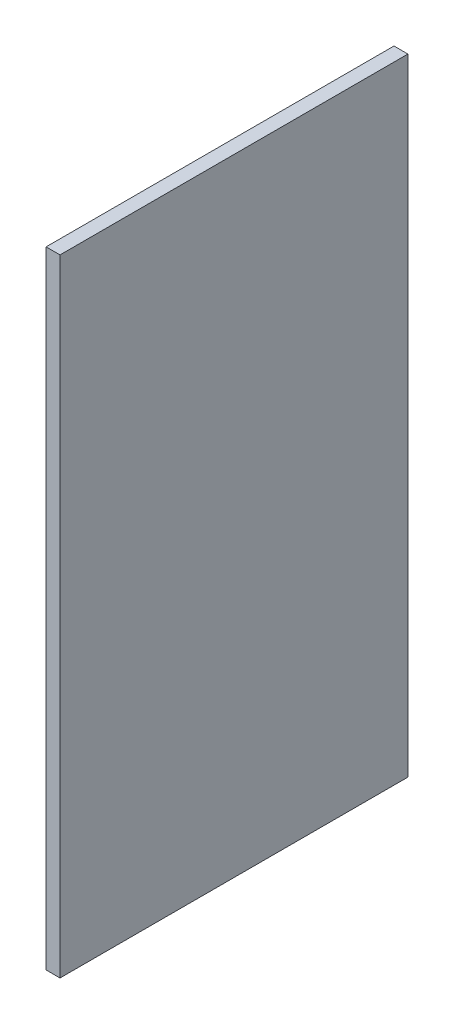
SolidWorks part; units mm, degrees
ref_plane "Front Plane" through (0, 0, 0) normal (0, 0, 1) x (1, 0, 0)
ref_plane "Top Plane" through (0, 0, 0) normal (0, 1, 0) x (1, 0, 0)
ref_plane "Right Plane" through (0, 0, 0) normal (1, 0, 0) x (0, 0, -1)
sketch "Sketch1" plane through (0, 0, 0) normal (1, 0, 0) x (0, 0, -1)
  line L1 (-26.6871, -32.1706) -> (-76.6871, -32.1706)
  line L2 (-26.6871, -32.1706) -> (-26.6871, 57.8294)
  line L3 (-26.6871, 57.8294) -> (-76.6871, 57.8294)
  line L4 (-76.6871, -32.1706) -> (-76.6871, 57.8294)
  dimension "Fin Heigth" = 90
  dimension "Fin Length" = 50
extrude "Boss-Extrude1" add sketch "Sketch1" along normal blind 2
